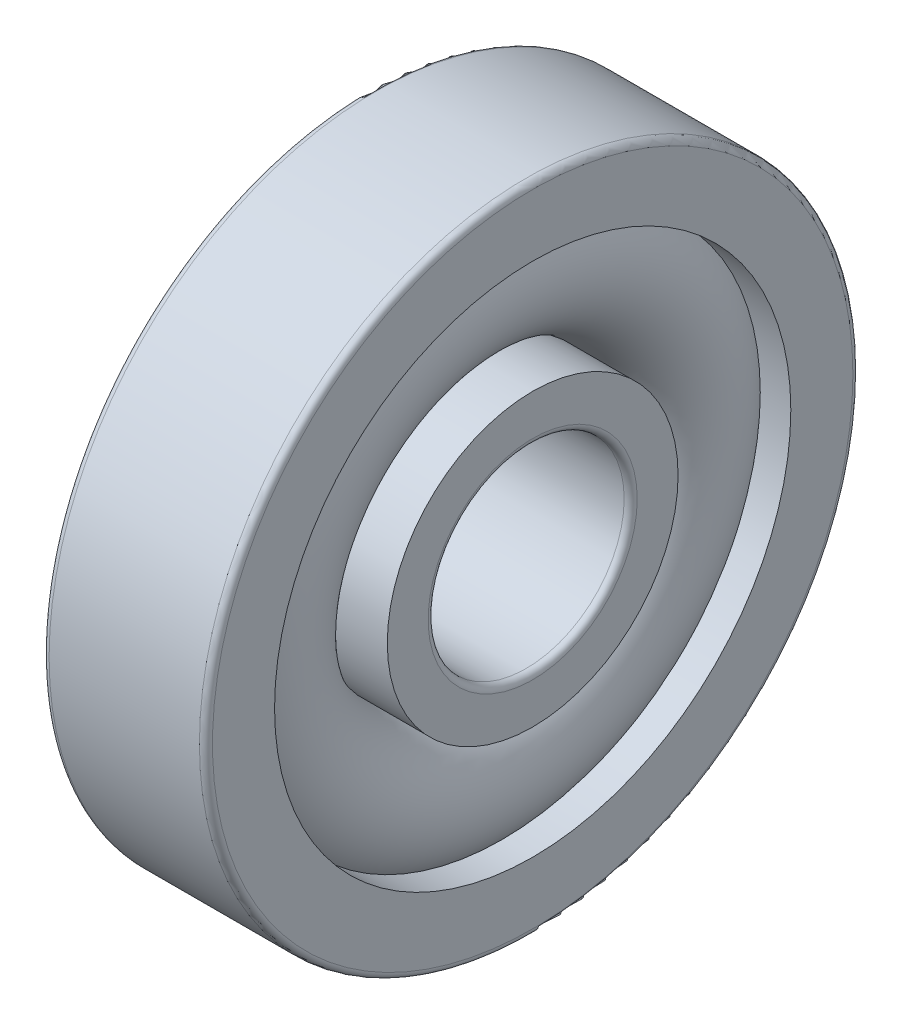
SolidWorks part; units mm, degrees
ref_plane "Plane1" through (0, 0, 0) normal (0, 0, 1) x (1, 0, 0)
ref_plane "Plane2" through (0, 0, 0) normal (0, 1, 0) x (1, 0, 0)
ref_plane "Plane3" through (0, 0, 0) normal (1, 0, 0) x (0, 0, -1)
sketch "Clipboard" plane through (0, 0, 0) normal (0, 0, 1) x (1, 0, 0)
  line L0 (-10, 0) -> (10, 0) construction
  line L1 (0, 0) -> (22.3471, -0.7804)
  line L2 (0, 0) -> (3.248, 0.1134)
  line L3 (0, 0) -> (22.3471, -0.7804)
  line L4 (0, 0) -> (-22.3573, -0.3902)
  dimension "BallCLRad" = 3.25
sketch "CagSpiSke" plane through (0, 0, 0) normal (0, 0, 1) x (1, 0, 0)
  line L0 (0.2625, 3.075) -> (0.2625, 3.425)
  line L1 (0.2625, 3.425) -> (-0.2625, 3.425)
  line L2 (-0.2625, 3.425) -> (-0.2625, 3.075)
  line L3 (-0.2625, 3.075) -> (0.2625, 3.075)
  line L4 (-20.6375, 0) -> (20.6375, 0) construction
  line L5 (0, 0) -> (0, 23.7692) construction
  dimension "OD" = 6.85
  dimension "ID" = 6.15
revolve "CageSpine" add sketch "CagSpiSke" angle 0.001 about L4
ref_axis "Axis1" through (-50, 0, 0) along (1, 0, 0)
sketch "CagBalSke" plane through (0, 0, 0) normal (0, 0, 1) x (1, 0, 0)
  line L0 (-1.155, 3.25) -> (1.155, 3.25)
  line L1 (-1.905, 3.25) -> (1.905, 3.25) construction
  line L2 (-10, 0) -> (10, 0) construction
  line L3 (0, 0) -> (0, 24) construction
  arc A0 (1.155, 3.25) -> (-1.155, 3.25) centre (0, 3.25) cw
  dimension "BallCLRad" = 3.25
revolve "CageBall" [suppressed] add sketch "CagBalSke" angle 360 about L1 reverse direction yes
pattern_circular "CageBalls" [suppressed] count 2 every 180 about axis through (-50, 0, 0) along (1, 0, 0)
sketch "CagTrmODSke" plane through (0, 0, 0) normal (0, 0, 1) x (1, 0, 0)
  line L0 (1.156, 3.425) -> (1.156, 4.406)
  line L1 (1.156, 4.406) -> (-1.156, 4.406)
  line L2 (-1.156, 4.406) -> (-1.156, 3.425)
  line L3 (-1.156, 3.425) -> (1.156, 3.425)
  line L4 (-20.6375, 0) -> (20.6375, 0) construction
  line L5 (0, 0) -> (0, 25) construction
  dimension "Width" = 2.312
  dimension "ID" = 6.85
  dimension "OD" = 8.812
revolve "CageTrimOD" [suppressed] cut sketch "CagTrmODSke" angle 360 about L4 reverse direction yes
sketch "CagTrmIDSke" plane through (0, 0, 0) normal (0, 0, 1) x (1, 0, 0)
  line L0 (1.156, 2.096) -> (1.156, 3.075)
  line L1 (1.156, 3.075) -> (-1.156, 3.075)
  line L2 (-1.156, 3.075) -> (-1.156, 2.096)
  line L3 (-1.156, 2.096) -> (1.156, 2.096)
  line L4 (-20.6375, 0) -> (20.6375, 0) construction
  line L5 (0, 0) -> (0, 25) construction
  dimension "Width" = 2.312
  dimension "ID" = 4.192
  dimension "OD" = 6.15
revolve "CageTrimID" [suppressed] cut sketch "CagTrmIDSke" angle 360 about L4 reverse direction yes
sketch "BalSimSke" plane through (0, 0, 0) normal (0, 0, 1) x (1, 0, 0)
  line L0 (-10, 0) -> (10, 0) construction
  line L1 (-10, 3.25) -> (10, 3.25) construction
  line L2 (0, 0) -> (0, 23) construction
  circle A0 centre (0, 3.25) radius 1.05
  dimension "BallCLRad" = 3.25
  dimension "Ball_diameter" = 2.1
revolve "BallsSimplified" add sketch "BalSimSke" angle 360 about L0
sketch "BalDetSke" plane through (0, 0, 0) normal (0, 0, 1) x (1, 0, 0)
  line L0 (-1.05, 3.25) -> (1.05, 3.25)
  line L1 (-1.905, 3.25) -> (1.905, 3.25) construction
  line L2 (0, 0) -> (0, 25) construction
  arc A0 (1.05, 3.25) -> (-1.05, 3.25) centre (0, 3.25) cw
  dimension "BallCLRad" = 3.25
  dimension "Ball_diameter" = 2.1
revolve "BallDetailed" [suppressed] add sketch "BalDetSke" angle 360 about L1 reverse direction yes
sketch "InnRacSke" plane through (0, 0, 0) normal (0, 0, 1) x (1, 0, 0)
  line L0 (-0.7487, 2.55) -> (-1.25, 2.55)
  line L1 (-1.25, 2.55) -> (-1.25, 1.6)
  line L2 (-1.15, 1.5) -> (1.15, 1.5)
  line L3 (1.25, 1.6) -> (1.25, 2.225)
  line L4 (0, 2.225) -> (1.25, 2.225)
  line L5 (-20.6375, 0) -> (20.6375, 0) construction
  line L6 (0, 0) -> (0, 30) construction
  arc A0 (-1.25, 1.6) -> (-1.15, 1.5) centre (-1.15, 1.6) ccw
  arc A1 (1.15, 1.5) -> (1.25, 1.6) centre (1.15, 1.6) ccw
  arc A2 (0, 2.225) -> (-0.7487, 2.55) centre (0, 3.25) cw
  dimension "BallCLRad" = 3.25
  dimension "Fillet_radius" = 0.1
  dimension "Ball_diameter" = 2.05
  dimension "ID" = 3
  dimension "OD" = 5.1
  dimension "Width" = 2.5
revolve "InnerRace" add sketch "InnRacSke" angle 360 about L5 reverse direction yes
sketch "OutRacSke" plane through (0, 0, 0) normal (0, 0, 1) x (1, 0, 0)
  line L0 (0, 4.275) -> (-1.25, 4.275)
  line L1 (-1.25, 4.275) -> (-1.25, 4.9)
  line L2 (-1.15, 5) -> (1.15, 5)
  line L3 (1.25, 4.9) -> (1.25, 3.95)
  line L4 (1.25, 3.95) -> (0.7487, 3.95)
  line L5 (-20.6375, 0) -> (20.6375, 0) construction
  line L6 (0, 0) -> (0, 30) construction
  arc A0 (-1.25, 4.9) -> (-1.15, 5) centre (-1.15, 4.9) cw
  arc A1 (1.15, 5) -> (1.25, 4.9) centre (1.15, 4.9) cw
  arc A2 (0.7487, 3.95) -> (0, 4.275) centre (0, 3.25) ccw
  dimension "BallCLRad" = 3.25
  dimension "Fillet_radius" = 0.1
  dimension "Ball_diameter" = 2.05
  dimension "Width" = 2.5
revolve "OuterRace" add sketch "OutRacSke" angle 360 about L5 reverse direction yes
pattern_circular "BallsDetailed" [suppressed] count 2 every 180 about axis through (-50, 0, 0) along (1, 0, 0)
equation "\"BallCLRad@Clipboard\" = ( \"OD@OutRacSke\" + \"ID@InnRacSke\" ) / 4"
equation "\"BallCLRad@BalSimSke\" = \"BallCLRad@Clipboard\""
equation "\"BallCLRad@BalDetSke\" = \"BallCLRad@Clipboard\""
equation "\"BallCLRad@InnRacSke\" = \"BallCLRad@Clipboard\""
equation "\"BallCLRad@OutRacSke\" = \"BallCLRad@Clipboard\""
equation "\"Ball_diameter@InnRacSke\" = \"Ball_diameter@BalDetSke\" - 0.05"
equation "\"Ball_diameter@OutRacSke\" = \"Ball_diameter@BalDetSke\" - 0.05"
equation "\"Ball_diameter@BalSimSke\" = \"Ball_diameter@BalDetSke\""
equation "\"Width@OutRacSke\" = \"Width@InnRacSke\""
equation "\"Fillet_radius@OutRacSke\" = \"Fillet_radius@InnRacSke\""
equation "\"Max_count@Clipboard\" = int( 3.14159265 / atn(( \"Ball_diameter@BalDetSke\" / 2) / sqr( \"BallCLRad@Clipboard\"  *  \"BallCLRad@Clipboard\" - ( \"Ball_diameter@BalDetSke\" / 2) *  ( \"Ball_diameter@BalDetSke\" / 2))))"
equation "\"Max_count@Clipboard\" = ((sgn( \"Max_count@Clipboard\" - \"Count@Clipboard\" )-1)*( \"Max_count@Clipboard\" - \"Count@Clipboard\" ))/-2+ \"Count@Clipboard\""
equation "\"Count@BallsDetailed\" = int( \"Show_count@Clipboard\" ) "
equation "\"Count@BallsDetailed\" = ((sgn( \"Count@BallsDetailed\" - \"Max_count@Clipboard\" )-1)*( \"Count@BallsDetailed\" - \"Max_count@Clipboard\" ))/-2+ \"Max_count@Clipboard\""
equation "\"Count@BallsDetailed\" = ((sgn( \"Count@BallsDetailed\" - \"Min_count@Clipboard\" )+1)*( \"Count@BallsDetailed\" - \"Min_count@Clipboard\"))/2 +\"Min_count@Clipboard\""
equation "\"Angle@BallsDetailed\" = 360.0 / \"Max_count@Clipboard\""
equation "\"BallCLRad@CagBalSke\" = \"BallCLRad@Clipboard\""
equation "\"Count@CageBalls\" = \"Count@BallsDetailed\""
equation "\"Angle@CageBalls\" = \"Angle@BallsDetailed\""
equation "\"Angle@CageSpine\" =  \"Angle@CageBalls\" * ( \"Count@CageBalls\" -1 + int( \"Count@CageBalls\" / \"Max_count@Clipboard\" ) )  + 0.001 -  int( \"Count@CageBalls\" / \"Max_count@Clipboard\" ) * 0.001"
equation "\"Angle@CageSpine\" =  \"Angle@CageSpine\" * int( \"Min_count@Clipboard\" / 2) + int(1 / \"Min_count@Clipboard\")  * 0.001"
equation "\"CageWallOD@CagBalSke\" =  \"Ball_diameter@BalDetSke\" * 1.1"
equation "\"Thickness@CagSpiSke\" =  \"Ball_diameter@BalDetSke\" * 0.25"
equation "\"OD@CagTrmODSke\" = \"BallCLRad@Clipboard\" * 2 + \"CageWallOD@CagBalSke\" + 0.002"
equation "\"ID@CagTrmODSke\" = \"BallCLRad@Clipboard\" * 2 + \"Ball_diameter@BalDetSke\" / 6"
equation "\"OD@CagTrmIDSke\" = \"BallCLRad@Clipboard\" * 2 - \"Ball_diameter@BalDetSke\" / 6"
equation "\"ID@CagTrmIDSke\" = \"BallCLRad@Clipboard\" * 2 - \"CageWallOD@CagBalSke\" + 0.002"
equation "\"OD@CagSpiSke\" = \"ID@CagTrmODSke\""
equation "\"ID@CagSpiSke\" = \"OD@CagTrmIDSke\""
equation "\"Width@CagTrmODSke\" = \"CageWallOD@CagBalSke\" + 0.002"
equation "\"Width@CagTrmIDSke\" = \"CageWallOD@CagBalSke\" + 0.002"
